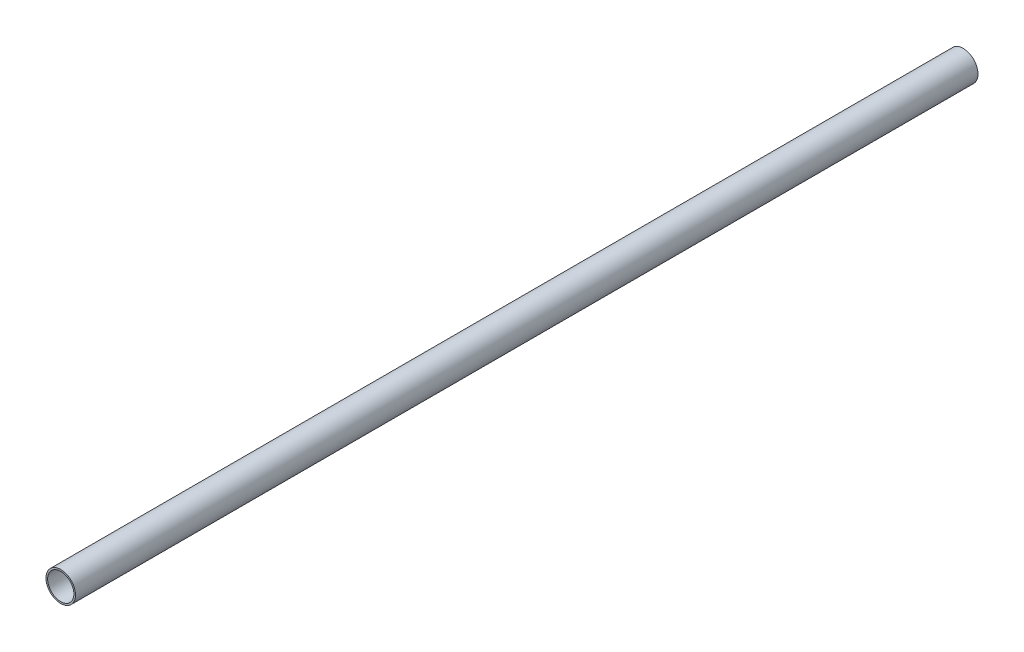
SolidWorks part; units mm, degrees
material "Carbon Fiber Tube - UD Approx"
ref_plane "Front Plane" through (0, 0, 0) normal (0, 0, 1) x (1, 0, 0)
ref_plane "Top Plane" through (0, 0, 0) normal (0, 1, 0) x (1, 0, 0)
ref_plane "Right Plane" through (0, 0, 0) normal (1, 0, 0) x (0, 0, -1)
sketch "Sketch1" plane through (0, 0, 0) normal (0, 0, 1) x (1, 0, 0)
  circle A0 centre (0, 0) radius 9
  circle A1 centre (0, 0) radius 8
  dimension "D1" = 18
  dimension "D2" = 16
extrude "Boss-Extrude1" add sketch "Sketch1" along normal blind 550
